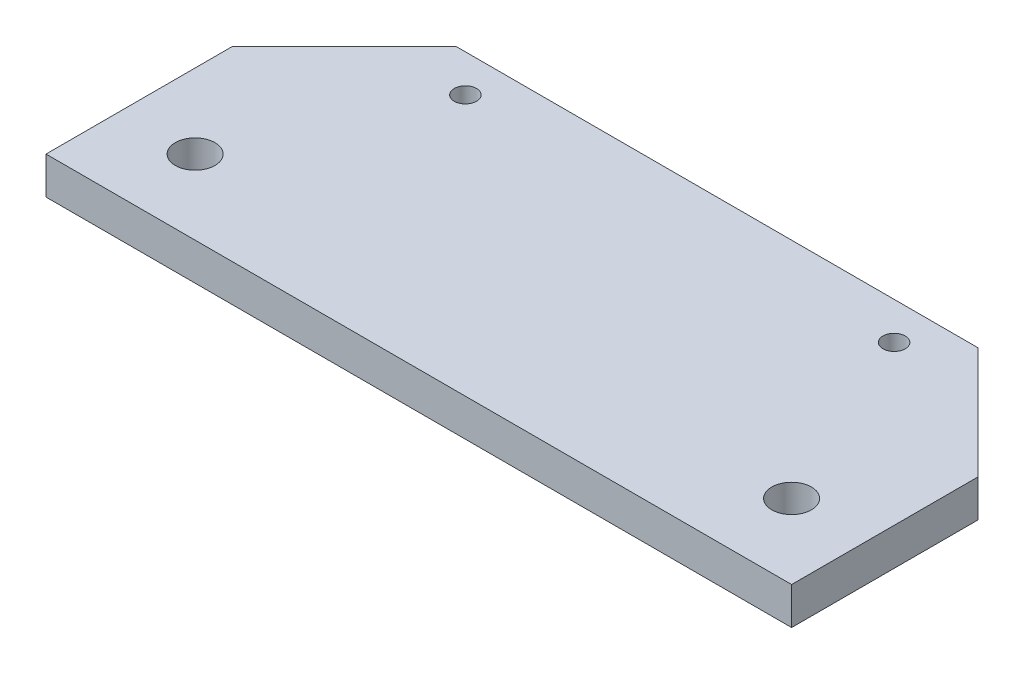
SolidWorks part; units mm, degrees
ref_plane "Front Plane" through (0, 0, 0) normal (0, 0, 1) x (1, 0, 0)
ref_plane "Top Plane" through (0, 0, 0) normal (0, 1, 0) x (1, 0, 0)
ref_plane "Right Plane" through (0, 0, 0) normal (1, 0, 0) x (0, 0, -1)
sketch "Sketch8" plane through (0, 0, 0) normal (0, 1, 0) x (1, 0, 0)
  line L0 (44.45, 0) -> (44.45, -12.7)
  line L1 (0, 0) -> (88.9, 0)
  line L2 (0, 0) -> (0, -12.7)
  line L3 (0, -12.7) -> (88.9, -12.7)
  line L4 (88.9, 0) -> (88.9, -12.7)
  line L5 (7.9375, -6.35) -> (80.9625, -6.35)
  line L6 (44.45, -12.7) -> (44.45, -38.1)
  line L7 (0, 0) -> (-19.05, -19.05)
  line L8 (-19.05, -19.05) -> (107.95, -19.05)
  line L9 (-19.05, -19.05) -> (-19.05, -57.15)
  line L10 (-19.05, -57.15) -> (107.95, -57.15)
  line L11 (107.95, -19.05) -> (107.95, -57.15)
  line L12 (-19.05, -19.05) -> (107.95, -57.15) construction
  line L13 (-19.05, -57.15) -> (107.95, -19.05) construction
  line L14 (88.9, 0) -> (107.95, -19.05)
  line L15 (95.25, -38.1) -> (-6.35, -38.1)
  point P10 (44.45, -6.35)
  point P23 (44.45, -38.1)
  dimension "D1" = 12.7
  dimension "D2" = 88.9
  dimension "D3" = 73.025
  dimension "D4" = 38.1
  dimension "D5" = 127
  dimension "D6" = 6.35
  dimension "D7" = 101.6
extrude "Boss-Extrude3" add sketch "Sketch8" along normal blind 6.35 contours L7 L8 L6 L3 L2 | L14 L4 L3 L6 L8 | L9 L8 L11 L10 | L2 L1 L4 L3 region at (11.0435, 0, 14.6326) region at (77.8565, 0, 14.6326)
hole_wizard "CBORE for #6 Socket Head Cap Screw1" positions "Sketch11" profile "Sketch12" counterbore size "#6" standard "ANSI Inch" end condition up to next
sketch "Sketch11" plane through (0, 0, 0) normal (0, -1, 0) x (-1, 0, 0)
  point P0 (-80.9625, -6.35)
  point P3 (-7.9375, -6.35)
sketch "Sketch12" plane through (80.9625, 0, 6.35) normal (1, 0, 0) x (0, 0, -1)
  line L0 (0, 0) -> (0, 6.35)
  line L1 (0, 6.35) -> (1.8986, 6.35)
  line L3 (1.8986, 6.35) -> (1.8986, 3.5052)
  line L4 (1.8986, 3.5052) -> (3.5725, 3.5052)
  line L5 (3.5725, 3.5052) -> (3.5725, 0)
  line L7 (3.5725, 0) -> (0, 0)
  line L11 (0, -6.35) -> (0, 107.95) construction
  dimension "Thru Hole Dia." = 3.7973
  dimension "Thru Hole Depth" = 6.35
  dimension "C'Bore Dia." = 7.145
  dimension "C'Bore Depth" = 3.5052
hole_wizard "1/4 Clearance Hole1" positions "Sketch13" profile "Sketch14" hole size "1/4" standard "ANSI Inch" end condition up to next
sketch "Sketch13" plane through (0, 6.35, 0) normal (0, 1, 0) x (1, 0, 0)
  point P0 (-6.35, -38.1)
  point P3 (95.25, -38.1)
sketch "Sketch14" plane through (-6.35, 6.35, 38.1) normal (1, 0, 0) x (0, 0, 1)
  line L0 (0, 0) -> (0, 6.35)
  line L1 (0, 6.35) -> (3.3782, 6.35)
  line L2 (3.3782, 6.35) -> (3.3782, 0)
  line L5 (3.3782, 0) -> (0, 0)
  line L11 (0, -6.35) -> (0, 107.95) construction
  dimension "Thru Hole Dia." = 6.7564
  dimension "Thru Hole Depth" = 6.35
ref_axis "Axis1" through (-6.35, 0, 38.1) along (0, 1, 0)
ref_axis "Axis2" through (95.25, 0, 38.1) along (0, 1, 0)
sketch "Sketch15" plane through (0, 0, 57.15) normal (0, 0, 1) x (1, 0, 0)
  line L0 (107.95, 6.35) -> (107.95, 0) construction
  line L1 (-19.05, 6.35) -> (-19.05, 0) construction
  line L2 (-19.05, 6.35) -> (107.95, 6.35) construction
  line L3 (-19.05, 0) -> (107.95, 0) construction
  line L4 (107.95, 6.35) -> (107.95, 0)
  line L5 (-19.05, 6.35) -> (-19.05, 0)
  line L6 (-19.05, 6.35) -> (107.95, 6.35)
  line L7 (-19.05, 0) -> (107.95, 0)
extrude "Cut-Extrude1" cut sketch "Sketch15" against normal blind 6.35
